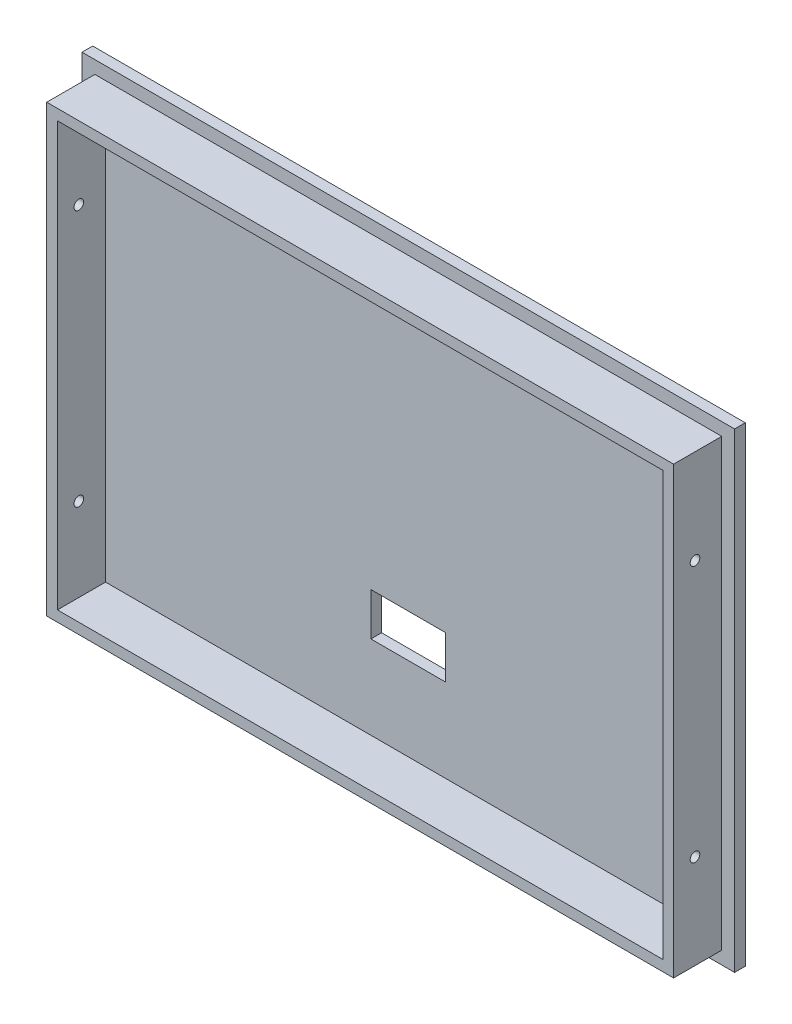
SolidWorks part; units mm, degrees
ref_plane "Front Plane" through (0, 0, 0) normal (0, 0, 1) x (1, 0, 0)
ref_plane "Top Plane" through (0, 0, 0) normal (0, 1, 0) x (1, 0, 0)
ref_plane "Right Plane" through (0, 0, 0) normal (1, 0, 0) x (0, 0, -1)
sketch "Sketch1" plane through (0, 0, 0) normal (0, 0, 1) x (1, 0, 0)
  line L1 (-61, 0) -> (61, 0)
  line L2 (-61, 0) -> (-61, 88)
  line L3 (-61, 88) -> (61, 88)
  line L4 (61, 0) -> (61, 88)
extrude "Boss-Extrude1" add sketch "Sketch1" along normal blind 2 from offset 2 offset against normal yes
sketch "Sketch2" plane through (0, 0, 0) normal (0, 0, 1) x (1, 0, 0)
  line L1 (-58.6, 2.4) -> (58.6, 2.4)
  line L2 (-58.6, 2.4) -> (-58.6, 85.6)
  line L3 (-58.6, 85.6) -> (58.6, 85.6)
  line L4 (58.6, 2.4) -> (58.6, 85.6)
extrude "Boss-Extrude2" add sketch "Sketch2" along normal blind 9.5 from offset 0.5 offset against normal yes
sketch "Sketch3" plane through (0, 0, 0) normal (0, 0, 1) x (1, 0, 0)
  line L1 (-56.6, 4.4) -> (56.6, 4.4)
  line L2 (-56.6, 4.4) -> (-56.6, 83.6)
  line L3 (-56.6, 83.6) -> (56.6, 83.6)
  line L4 (56.6, 4.4) -> (56.6, 83.6)
extrude "Boss-Extrude3" add sketch "Sketch3" along normal blind 10 separate body
combine bodies "Combine1" operation type subtract main body 102 bodies to subtract 103
sketch "Sketch4" plane through (0, 0, 0) normal (0, 0, 1) x (1, 0, 0)
  line L1 (-7, 20) -> (7, 20)
  line L2 (-7, 20) -> (-7, 28)
  line L3 (-7, 28) -> (7, 28)
  line L4 (7, 20) -> (7, 28)
extrude "Boss-Extrude4" add sketch "Sketch4" along normal blind 4 from offset 3 separate body offset against normal yes
combine bodies "Combine2" operation type subtract main body 104 bodies to subtract 105
sketch "Sketch5" plane through (0, 0, 0) normal (1, 0, 0) x (0, 0, -1)
  circle A0 centre (-5, 20) radius 0.9
extrude "Boss-Extrude5" add sketch "Sketch5" along normal blind 130 from offset 65 separate body offset against normal yes
combine bodies "Combine3" operation type subtract main body 106 bodies to subtract 107
sketch "Sketch6" plane through (0, 0, 0) normal (1, 0, 0) x (0, 0, -1)
  circle A0 centre (-5, 68) radius 0.9
extrude "Boss-Extrude6" add sketch "Sketch6" along normal blind 130 from offset 65 separate body offset against normal yes
combine bodies "Combine4" operation type subtract main body 108 bodies to subtract 109
